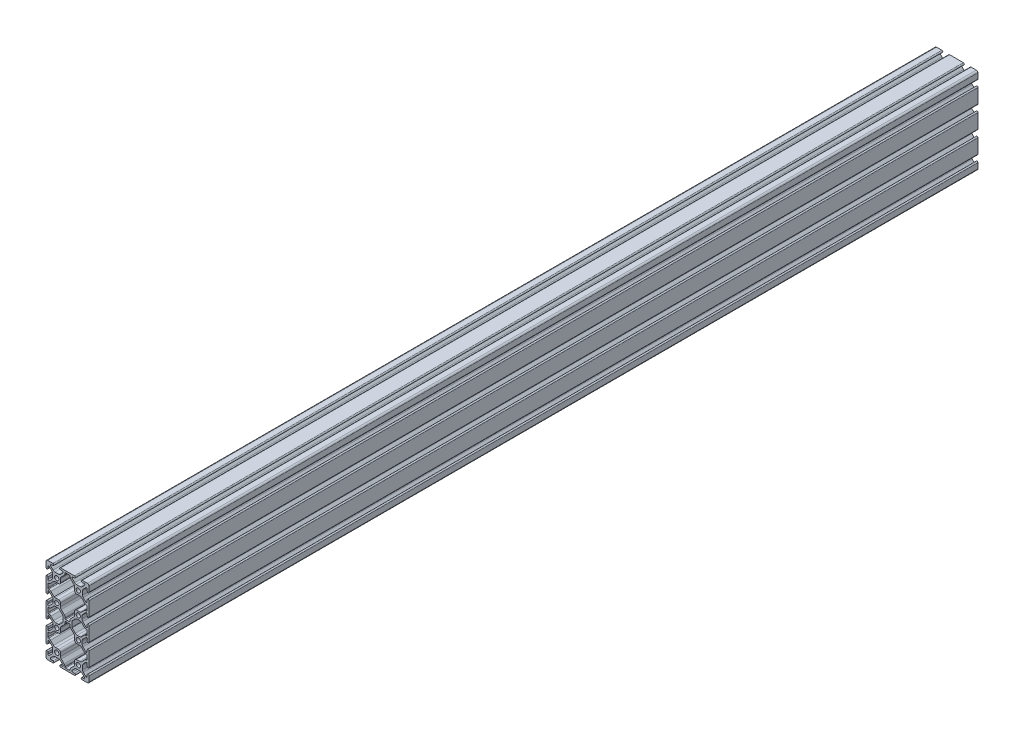
SolidWorks part; units mm, degrees
material "6061 Alloy"
ref_plane "Front Plane" through (0, 0, 0) normal (0, 0, 1) x (1, 0, 0)
ref_plane "Top Plane" through (0, 0, 0) normal (0, 1, 0) x (1, 0, 0)
ref_plane "Right Plane" through (0, 0, 0) normal (1, 0, 0) x (0, 0, -1)
sketch "Sketch1" plane through (0, 0, 0) normal (0, 0, 1) x (1, 0, 0)
  line L0 (-25.6036, 0) -> (0, 0) construction
  line L1 (-8.2025, 43.3108) -> (-5.2383, 46.275)
  line L2 (-25, 3.77) -> (-25, -3.77)
  line L3 (-8.1858, 12.4875) -> (-8.1858, 11.0114)
  line L4 (8.1878, 11.0114) -> (8.1878, 14.5891)
  line L5 (3.7569, 4.9667) -> (7.2705, 8.4802)
  line L6 (14.3225, 16.7991) -> (10.3978, 16.7991)
  line L7 (15.6024, 17.1021) -> (19.2982, 20.7979)
  line L8 (22.1127, 21.7264) -> (21.5397, 21.7264)
  line L9 (-2.3158, 50) -> (2.3158, 50)
  line L10 (22.8749, 26.8568) -> (22.8749, 22.4886)
  line L11 (21.8715, 27.6122) -> (22.1256, 27.6122)
  line L12 (19.7762, 28.7106) -> (16.3874, 32.0994)
  line L13 (13.8398, 33.0305) -> (10.3624, 33.0305)
  line L14 (8.1524, 39.0512) -> (8.1524, 35.2405)
  line L15 (7.2223, 41.2645) -> (4.0122, 44.4746)
  line L16 (3.0895, 47.0978) -> (3.0895, 46.7023)
  line L17 (-22.86, 2.484) -> (-22.86, -2.484)
  line L18 (-5.137, 3.0639) -> (-5.137, -3.0639)
  line L19 (5.137, 3.0639) -> (5.137, -3.0639)
  line L20 (22.86, 2.484) -> (22.86, -2.484)
  line L21 (-5.328, 3.5248) -> (-8.9952, 7.192)
  line L22 (-14.0474, 8.1222) -> (-11.2408, 8.1222)
  line L23 (-16.2931, 7.192) -> (-19.3292, 4.1559)
  line L24 (25, 3.77) -> (25, -3.77)
  line L25 (-22.0978, 3.2462) -> (-21.8437, 3.2462)
  line L26 (-10.3899, 33.0305) -> (-10.3624, 33.0305)
  line L27 (-8.1858, 12.4875) -> (-8.1858, 14.5891)
  line L28 (-8.1524, 39.0512) -> (-8.1524, 35.2405)
  line L29 (-25.6036, -25) -> (3.1162, -25) construction
  line L30 (-12.5, -37.5) -> (-12.5, -51.8721) construction
  line L31 (8.2025, -43.3108) -> (5.2383, -46.275)
  line L32 (-2.8325, -2.6943) -> (-2.8325, -1.8197)
  line L33 (-2.0703, -1.0575) -> (2.0723, -1.0575)
  line L34 (2.8345, -2.6943) -> (2.8345, -1.8197)
  line L35 (-3.7549, -4.9667) -> (-7.2685, -8.4802)
  line L36 (-14.3205, -16.7991) -> (-10.3958, -16.7991)
  line L37 (-15.6004, -17.1021) -> (-19.2962, -20.7979)
  line L38 (-22.1107, -21.7264) -> (-21.5377, -21.7264)
  line L39 (-22.8729, -26.8568) -> (-22.8729, -22.4886)
  line L40 (-22.1107, -27.619) -> (-21.8566, -27.619)
  line L41 (5.328, -3.5248) -> (8.9952, -7.192)
  line L42 (11.2408, -8.1222) -> (14.0474, -8.1222)
  line L43 (16.2931, -7.192) -> (19.3292, -4.1559)
  line L44 (-19.7762, -28.7106) -> (-16.3874, -32.0994)
  line L45 (22.0978, -3.2462) -> (21.8437, -3.2462)
  line L46 (-13.8398, -33.0305) -> (-10.3899, -33.0305)
  line L47 (-7.2223, -41.2645) -> (-4.0122, -44.4746)
  line L48 (5.8948, -47.86) -> (8.0244, -47.86)
  line L49 (-8.0244, 50) -> (-2.3158, 50)
  line L50 (-8.0244, 47.86) -> (-5.8948, 47.86)
  line L51 (0, 47.86) -> (2.3273, 47.86)
  line L52 (-3.0895, -47.0978) -> (-3.0895, -46.7023)
  line L53 (-14.7082, 42.4485) -> (-10.2843, 42.4484)
  line L54 (-16.7975, 43.3108) -> (-19.7617, 46.275)
  line L55 (-19.1052, 47.86) -> (-16.9756, 47.86)
  line L56 (-23.0411, 50) -> (-16.9756, 50)
  line L57 (2.3158, 50) -> (8.0244, 50)
  line L58 (-25, 42.0822) -> (-25, 48.3182)
  line L59 (10.2843, -42.4484) -> (14.7082, -42.4485)
  line L60 (-22.86, 42.0822) -> (-22.86, 44.2118)
  line L61 (-21.1643, 44.6511) -> (-18.3279, 41.8147)
  line L62 (-17.3977, 39.5691) -> (-17.3977, 35.4309)
  line L63 (-18.3279, 33.1853) -> (-21.1271, 30.3861)
  line L64 (-22.86, 31.1039) -> (-22.86, 33.4422)
  line L65 (-25, 33.4422) -> (-25, 29.299)
  line L66 (-25, 21.2197) -> (-25, 29.299)
  line L67 (-25, 17.0404) -> (-25, 21.2197)
  line L68 (-22.8665, 17.0958) -> (-22.8665, 19.4894)
  line L69 (-21.2483, 19.7351) -> (-17.927, 16.4138)
  line L70 (-16.865, 11.3738) -> (-16.865, 14.4803)
  line L71 (-17.7378, 8.7737) -> (-21.0608, 5.4507)
  line L72 (-22.8659, 6.4893) -> (-22.8659, 8.2661)
  line L73 (-25, 3.77) -> (-25, 8.2776)
  line L74 (16.7975, -43.3108) -> (19.7617, -46.275)
  line L75 (19.1052, -47.86) -> (16.9756, -47.86)
  line L76 (16.9756, -50) -> (21.7588, -50)
  line L77 (21.7588, -50) -> (23.0411, -50)
  line L78 (25, -42.0822) -> (25, -48.3182)
  line L79 (22.86, -42.0822) -> (22.86, -44.2118)
  line L80 (21.1643, -44.6511) -> (18.3279, -41.8147)
  line L81 (17.3977, -39.5691) -> (17.3977, -35.4309)
  line L82 (18.3279, -33.1853) -> (21.1271, -30.3861)
  line L83 (25, -33.4422) -> (25, -29.299)
  line L84 (22.86, -31.1039) -> (22.86, -33.4422)
  line L85 (-2.3273, -47.86) -> (0, -47.86)
  line L86 (22.8665, -17.0958) -> (22.8665, -19.4894)
  line L87 (21.2483, -19.7351) -> (17.927, -16.4138)
  line L88 (16.865, -11.3738) -> (16.865, -14.4803)
  line L89 (17.7378, -8.7737) -> (21.0608, -5.4507)
  line L90 (22.8659, -6.4893) -> (22.8659, -8.2661)
  line L91 (25, -21.2197) -> (25, -29.299)
  line L92 (25, -17.0404) -> (25, -21.2197)
  line L93 (25, -3.77) -> (25, -8.2776)
  line L94 (-25, -3.77) -> (-25, -8.2776)
  line L95 (-12.5, 37.5) -> (-12.5, 51.8721) construction
  line L96 (-25.6036, 25) -> (3.1162, 25) construction
  line L97 (-22.8659, -6.4893) -> (-22.8659, -8.2661)
  line L98 (-17.7378, -8.7737) -> (-21.0608, -5.4507)
  line L99 (-16.865, -11.3738) -> (-16.865, -14.4803)
  line L100 (-21.2483, -19.7351) -> (-17.927, -16.4138)
  line L101 (-22.8665, -17.0958) -> (-22.8665, -19.4894)
  line L102 (-25, -17.0404) -> (-25, -21.2197)
  line L103 (-25, -21.2197) -> (-25, -29.299)
  line L104 (-25, -33.4422) -> (-25, -29.299)
  line L105 (-22.86, -31.1039) -> (-22.86, -33.4422)
  line L106 (25, 3.77) -> (25, 8.2776)
  line L107 (25, 17.0404) -> (25, 21.2197)
  line L108 (-18.3279, -33.1853) -> (-21.1271, -30.3861)
  line L109 (-17.3977, -39.5691) -> (-17.3977, -35.4309)
  line L110 (-21.1643, -44.6511) -> (-18.3279, -41.8147)
  line L111 (-22.86, -42.0822) -> (-22.86, -44.2118)
  line L112 (-25, -42.0822) -> (-25, -48.3182)
  line L113 (25, 21.2197) -> (25, 29.299)
  line L114 (2.3158, -50) -> (8.0244, -50)
  line L115 (-23.0411, -50) -> (-16.9756, -50)
  line L116 (22.8659, 6.4893) -> (22.8659, 8.2661)
  line L117 (17.7378, 8.7737) -> (21.0608, 5.4507)
  line L118 (16.865, 11.3738) -> (16.865, 14.4803)
  line L119 (21.2483, 19.7351) -> (17.927, 16.4138)
  line L120 (22.8665, 17.0958) -> (22.8665, 19.4894)
  line L121 (-2.3273, 47.86) -> (0, 47.86)
  line L122 (22.86, 31.1039) -> (22.86, 33.4422)
  line L123 (25, 33.4422) -> (25, 29.299)
  line L124 (-19.1052, -47.86) -> (-16.9756, -47.86)
  line L125 (18.3279, 33.1853) -> (21.1271, 30.3861)
  line L126 (17.3977, 39.5691) -> (17.3977, 35.4309)
  line L127 (21.1643, 44.6511) -> (18.3279, 41.8147)
  line L128 (22.86, 42.0822) -> (22.86, 44.2118)
  line L129 (25, 42.0822) -> (25, 48.3182)
  line L130 (-16.7975, -43.3108) -> (-19.7617, -46.275)
  line L131 (21.7588, 50) -> (23.0411, 50)
  line L132 (16.9756, 50) -> (21.7588, 50)
  line L133 (19.1052, 47.86) -> (16.9756, 47.86)
  line L134 (16.7975, 43.3108) -> (19.7617, 46.275)
  line L135 (10.2843, 42.4484) -> (14.7082, 42.4485)
  line L136 (-14.7082, -42.4485) -> (-10.2843, -42.4484)
  line L137 (-3.0895, 47.0978) -> (-3.0895, 46.7023)
  line L138 (5.8948, 47.86) -> (8.0244, 47.86)
  line L139 (0, -47.86) -> (2.3273, -47.86)
  line L140 (-8.0244, -47.86) -> (-5.8948, -47.86)
  line L141 (-8.0244, -50) -> (-2.3158, -50)
  line L142 (-8.1524, -39.0512) -> (-8.1524, -35.2405)
  line L143 (-8.1858, -12.4875) -> (-8.1858, -14.5891)
  line L144 (-10.3899, -33.0305) -> (-10.3624, -33.0305)
  line L145 (-22.0978, -3.2462) -> (-21.8437, -3.2462)
  line L146 (-16.2931, -7.192) -> (-19.3292, -4.1559)
  line L147 (-14.0474, -8.1222) -> (-11.2408, -8.1222)
  line L148 (-5.328, -3.5248) -> (-8.9952, -7.192)
  line L149 (3.0895, -47.0978) -> (3.0895, -46.7023)
  line L150 (7.2223, -41.2645) -> (4.0122, -44.4746)
  line L151 (8.1524, -39.0512) -> (8.1524, -35.2405)
  line L152 (13.8398, -33.0305) -> (10.3624, -33.0305)
  line L153 (19.7762, -28.7106) -> (16.3874, -32.0994)
  line L154 (-7.2223, 41.2645) -> (-4.0122, 44.4746)
  line L155 (21.8715, -27.6122) -> (22.1256, -27.6122)
  line L156 (22.8749, -26.8568) -> (22.8749, -22.4886)
  line L157 (-2.3158, -50) -> (2.3158, -50)
  line L158 (22.1127, -21.7264) -> (21.5397, -21.7264)
  line L159 (15.6024, -17.1021) -> (19.2982, -20.7979)
  line L160 (-13.8398, 33.0305) -> (-10.3899, 33.0305)
  line L161 (14.3225, -16.7991) -> (10.3978, -16.7991)
  line L162 (22.0978, 3.2462) -> (21.8437, 3.2462)
  line L163 (-19.7762, 28.7106) -> (-16.3874, 32.0994)
  line L164 (16.2931, 7.192) -> (19.3292, 4.1559)
  line L165 (11.2408, 8.1222) -> (14.0474, 8.1222)
  line L166 (5.328, 3.5248) -> (8.9952, 7.192)
  line L167 (3.7569, -4.9667) -> (7.2705, -8.4802)
  line L168 (8.1878, -11.0114) -> (8.1878, -14.5891)
  line L169 (-8.1858, -12.4875) -> (-8.1858, -11.0114)
  line L170 (-8.2025, -43.3108) -> (-5.2383, -46.275)
  line L171 (-22.1107, 27.619) -> (-21.8566, 27.619)
  line L172 (-22.8729, 26.8568) -> (-22.8729, 22.4886)
  line L173 (-22.1107, 21.7264) -> (-21.5377, 21.7264)
  line L174 (-15.6004, 17.1021) -> (-19.2962, 20.7979)
  line L175 (-14.3205, 16.7991) -> (-10.3958, 16.7991)
  line L176 (-3.7549, 4.9667) -> (-7.2685, 8.4802)
  line L177 (2.8345, 2.6943) -> (2.8345, 1.8197)
  line L178 (-2.0703, 1.0575) -> (2.0723, 1.0575)
  line L179 (-2.8325, 2.6943) -> (-2.8325, 1.8197)
  line L180 (25, 0) -> (0, 0) construction
  line L184 (8.2025, 43.3108) -> (5.2383, 46.275)
  arc A0 (-8.1858, 14.5891) -> (-10.3958, 16.7991) centre (-10.3958, 14.5891) ccw
  arc A1 (-8.1524, 35.2405) -> (-10.3624, 33.0305) centre (-10.3624, 35.2405) cw
  arc A2 (10.3978, 16.7991) -> (8.1878, 14.5891) centre (10.3978, 14.5891) ccw
  circle A3 centre (-12.5, 12.5) radius 2.5
  circle A4 centre (-12.5, 37.5) radius 2.5
  arc A5 (7.2705, 8.4802) -> (8.1878, 11.0114) centre (5.0248, 10.7259) ccw
  arc A6 (10.3624, 33.0305) -> (8.1524, 35.2405) centre (10.3624, 35.2405) cw
  arc A7 (14.3225, 16.7991) -> (15.6024, 17.1021) centre (14.2466, 19.974) ccw
  arc A8 (21.5397, 21.7264) -> (19.2982, 20.7979) centre (21.5397, 18.5564) ccw
  arc A9 (22.1127, 21.7264) -> (22.8749, 22.4886) centre (22.1127, 22.4886) ccw
  arc A10 (22.8749, 26.8568) -> (22.1256, 27.6122) centre (22.1127, 26.8501) ccw
  arc A11 (-8.0244, 47.86) -> (-8.0244, 50) centre (-8.0244, 48.93) cw
  arc A12 (19.7762, 28.7106) -> (21.8715, 27.6122) centre (22.1894, 30.7662) ccw
  arc A13 (16.3874, 32.0994) -> (13.8398, 33.0305) centre (13.8398, 29.0797) ccw
  circle A14 centre (12.5, -12.5) radius 2.5
  arc A15 (8.1524, 39.0512) -> (7.2223, 41.2645) centre (4.9767, 39.0188) ccw
  arc A16 (3.0895, 47.0978) -> (2.3273, 47.86) centre (2.3273, 47.0978) ccw
  arc A17 (3.0895, 46.7023) -> (4.0122, 44.4746) centre (6.2399, 46.7023) ccw
  arc A18 (-3.0895, 47.0978) -> (-2.3273, 47.86) centre (-2.3273, 47.0978) cw
  circle A19 centre (12.5, -37.5) radius 2.5
  arc A20 (-3.7549, -4.9667) -> (-2.8325, -2.6943) centre (-5.9826, -2.739) ccw
  arc A21 (-5.137, 3.0639) -> (-5.328, 3.5248) centre (-5.7889, 3.0639) ccw
  arc A22 (-8.9952, 7.192) -> (-11.2408, 8.1222) centre (-11.2408, 4.9464) ccw
  arc A23 (-14.0474, 8.1222) -> (-16.2931, 7.192) centre (-14.0474, 4.9464) ccw
  arc A24 (-21.8437, 3.2462) -> (-19.3292, 4.1559) centre (-21.5569, 6.3836) ccw
  arc A25 (-22.0978, 3.2462) -> (-22.86, 2.484) centre (-22.0978, 2.484) ccw
  arc A26 (-2.0703, -1.0575) -> (-2.8325, -1.8197) centre (-2.0703, -1.8197) ccw
  arc A27 (2.0723, -1.0575) -> (2.8345, -1.8197) centre (2.0723, -1.8197) cw
  arc A28 (3.7569, -4.9667) -> (2.8345, -2.6943) centre (5.9846, -2.739) cw
  arc A29 (-7.2685, -8.4802) -> (-8.1858, -11.0114) centre (-5.0228, -10.7259) ccw
  arc A30 (8.0244, -47.86) -> (8.0244, -50) centre (8.0244, -48.93) cw
  arc A31 (-14.3205, -16.7991) -> (-15.6004, -17.1021) centre (-14.2446, -19.974) ccw
  arc A32 (-21.5377, -21.7264) -> (-19.2962, -20.7979) centre (-21.5377, -18.5564) ccw
  arc A33 (-22.1107, -21.7264) -> (-22.8729, -22.4886) centre (-22.1107, -22.4886) ccw
  arc A34 (-22.8729, -26.8568) -> (-22.1107, -27.619) centre (-22.1107, -26.8568) ccw
  arc A35 (-19.7762, -28.7106) -> (-21.8566, -27.619) centre (-22.1844, -30.772) ccw
  arc A36 (-16.3874, -32.0994) -> (-13.8398, -33.0305) centre (-13.8398, -29.0797) ccw
  arc A37 (5.137, -3.0639) -> (5.328, -3.5248) centre (5.7889, -3.0639) ccw
  arc A38 (8.9952, -7.192) -> (11.2408, -8.1222) centre (11.2408, -4.9464) ccw
  arc A39 (14.0474, -8.1222) -> (16.2931, -7.192) centre (14.0474, -4.9464) ccw
  arc A40 (21.8437, -3.2462) -> (19.3292, -4.1559) centre (21.5569, -6.3836) ccw
  arc A41 (22.0978, -3.2462) -> (22.86, -2.484) centre (22.0978, -2.484) ccw
  arc A42 (5.8948, -47.86) -> (5.2383, -46.275) centre (5.8948, -46.9315) cw
  arc A43 (-8.1524, -39.0512) -> (-7.2223, -41.2645) centre (-4.9767, -39.0188) ccw
  arc A44 (10.2843, -42.4484) -> (8.2025, -43.3108) centre (10.2843, -45.3926) ccw
  arc A45 (16.7975, -43.3108) -> (14.7082, -42.4485) centre (14.7157, -45.3926) ccw
  arc A46 (19.1052, -47.86) -> (19.7617, -46.275) centre (19.1052, -46.9315) ccw
  arc A47 (16.9756, -47.86) -> (16.9756, -50) centre (16.9756, -48.93) ccw
  arc A48 (-5.8948, 47.86) -> (-5.2383, 46.275) centre (-5.8948, 46.9315) cw
  arc A49 (-3.0895, 46.7023) -> (-4.0122, 44.4746) centre (-6.2399, 46.7023) cw
  arc A50 (-10.2843, 42.4484) -> (-8.2025, 43.3108) centre (-10.2843, 45.3926) ccw
  arc A51 (-16.7975, 43.3108) -> (-14.7082, 42.4485) centre (-14.7157, 45.3926) ccw
  arc A52 (-19.1052, 47.86) -> (-19.7617, 46.275) centre (-19.1052, 46.9315) ccw
  arc A53 (-16.9756, 47.86) -> (-16.9756, 50) centre (-16.9756, 48.93) ccw
  arc A54 (-23.0411, 50) -> (-25, 48.3182) centre (-23.0411, 48.0183) ccw
  arc A55 (-25, 42.0822) -> (-22.86, 42.0822) centre (-23.93, 42.0822) ccw
  arc A56 (-21.1643, 44.6511) -> (-22.86, 44.2118) centre (-21.8829, 43.9325) ccw
  arc A57 (-17.3977, 39.5691) -> (-18.3279, 41.8147) centre (-20.5736, 39.5691) ccw
  arc A58 (-18.3279, 33.1853) -> (-17.3977, 35.4309) centre (-20.5736, 35.4309) ccw
  arc A59 (-22.86, 31.1039) -> (-21.1271, 30.3861) centre (-21.8449, 31.1039) ccw
  arc A60 (-22.86, 33.4422) -> (-25, 33.4422) centre (-23.93, 33.4422) ccw
  arc A61 (-25, 17.0404) -> (-22.8665, 17.0958) centre (-23.9321, 17.0236) ccw
  arc A62 (-21.2483, 19.7351) -> (-22.8665, 19.4894) centre (-21.9669, 19.0165) ccw
  arc A63 (-16.865, 14.4803) -> (-17.927, 16.4138) centre (-20.0063, 14.0133) ccw
  arc A64 (-17.7378, 8.7737) -> (-16.865, 11.3738) centre (-20.017, 10.9853) ccw
  arc A65 (-22.8659, 6.4893) -> (-21.0608, 5.4507) centre (-21.9633, 5.97) ccw
  arc A66 (-22.8659, 8.2661) -> (-25, 8.2776) centre (-23.9329, 8.2719) ccw
  arc A67 (23.0411, -50) -> (25, -48.3182) centre (23.0411, -48.0183) ccw
  arc A68 (25, -42.0822) -> (22.86, -42.0822) centre (23.93, -42.0822) ccw
  arc A69 (21.1643, -44.6511) -> (22.86, -44.2118) centre (21.8829, -43.9325) ccw
  arc A70 (17.3977, -39.5691) -> (18.3279, -41.8147) centre (20.5736, -39.5691) ccw
  arc A71 (18.3279, -33.1853) -> (17.3977, -35.4309) centre (20.5736, -35.4309) ccw
  arc A72 (22.86, -31.1039) -> (21.1271, -30.3861) centre (21.8449, -31.1039) ccw
  arc A73 (22.86, -33.4422) -> (25, -33.4422) centre (23.93, -33.4422) ccw
  arc A74 (25, -17.0404) -> (22.8665, -17.0958) centre (23.9321, -17.0236) ccw
  arc A75 (21.2483, -19.7351) -> (22.8665, -19.4894) centre (21.9669, -19.0165) ccw
  arc A76 (16.865, -14.4803) -> (17.927, -16.4138) centre (20.0063, -14.0133) ccw
  arc A77 (17.7378, -8.7737) -> (16.865, -11.3738) centre (20.017, -10.9853) ccw
  arc A78 (22.8659, -6.4893) -> (21.0608, -5.4507) centre (21.9633, -5.97) ccw
  arc A79 (22.8659, -8.2661) -> (25, -8.2776) centre (23.9329, -8.2719) ccw
  arc A80 (-22.8659, -8.2661) -> (-25, -8.2776) centre (-23.9329, -8.2719) cw
  arc A81 (-22.8659, -6.4893) -> (-21.0608, -5.4507) centre (-21.9633, -5.97) cw
  arc A82 (-17.7378, -8.7737) -> (-16.865, -11.3738) centre (-20.017, -10.9853) cw
  arc A83 (-16.865, -14.4803) -> (-17.927, -16.4138) centre (-20.0063, -14.0133) cw
  arc A84 (-21.2483, -19.7351) -> (-22.8665, -19.4894) centre (-21.9669, -19.0165) cw
  arc A85 (-25, -17.0404) -> (-22.8665, -17.0958) centre (-23.9321, -17.0236) cw
  arc A86 (-22.86, -33.4422) -> (-25, -33.4422) centre (-23.93, -33.4422) cw
  arc A87 (-22.86, -31.1039) -> (-21.1271, -30.3861) centre (-21.8449, -31.1039) cw
  arc A88 (-18.3279, -33.1853) -> (-17.3977, -35.4309) centre (-20.5736, -35.4309) cw
  arc A89 (-17.3977, -39.5691) -> (-18.3279, -41.8147) centre (-20.5736, -39.5691) cw
  arc A90 (-21.1643, -44.6511) -> (-22.86, -44.2118) centre (-21.8829, -43.9325) cw
  arc A91 (-25, -42.0822) -> (-22.86, -42.0822) centre (-23.93, -42.0822) cw
  arc A92 (-23.0411, -50) -> (-25, -48.3182) centre (-23.0411, -48.0183) cw
  arc A93 (22.8659, 8.2661) -> (25, 8.2776) centre (23.9329, 8.2719) cw
  arc A94 (22.8659, 6.4893) -> (21.0608, 5.4507) centre (21.9633, 5.97) cw
  arc A95 (17.7378, 8.7737) -> (16.865, 11.3738) centre (20.017, 10.9853) cw
  arc A96 (16.865, 14.4803) -> (17.927, 16.4138) centre (20.0063, 14.0133) cw
  arc A97 (21.2483, 19.7351) -> (22.8665, 19.4894) centre (21.9669, 19.0165) cw
  arc A98 (25, 17.0404) -> (22.8665, 17.0958) centre (23.9321, 17.0236) cw
  arc A99 (22.86, 33.4422) -> (25, 33.4422) centre (23.93, 33.4422) cw
  arc A100 (22.86, 31.1039) -> (21.1271, 30.3861) centre (21.8449, 31.1039) cw
  arc A101 (18.3279, 33.1853) -> (17.3977, 35.4309) centre (20.5736, 35.4309) cw
  arc A102 (17.3977, 39.5691) -> (18.3279, 41.8147) centre (20.5736, 39.5691) cw
  arc A103 (21.1643, 44.6511) -> (22.86, 44.2118) centre (21.8829, 43.9325) cw
  arc A104 (25, 42.0822) -> (22.86, 42.0822) centre (23.93, 42.0822) cw
  arc A105 (23.0411, 50) -> (25, 48.3182) centre (23.0411, 48.0183) cw
  arc A106 (16.9756, 47.86) -> (16.9756, 50) centre (16.9756, 48.93) cw
  arc A107 (19.1052, 47.86) -> (19.7617, 46.275) centre (19.1052, 46.9315) cw
  arc A108 (16.7975, 43.3108) -> (14.7082, 42.4485) centre (14.7157, 45.3926) cw
  arc A109 (10.2843, 42.4484) -> (8.2025, 43.3108) centre (10.2843, 45.3926) cw
  arc A110 (-8.1524, 39.0512) -> (-7.2223, 41.2645) centre (-4.9767, 39.0188) cw
  arc A111 (5.8948, 47.86) -> (5.2383, 46.275) centre (5.8948, 46.9315) ccw
  arc A112 (-16.9756, -47.86) -> (-16.9756, -50) centre (-16.9756, -48.93) cw
  arc A113 (-19.1052, -47.86) -> (-19.7617, -46.275) centre (-19.1052, -46.9315) cw
  arc A114 (-16.7975, -43.3108) -> (-14.7082, -42.4485) centre (-14.7157, -45.3926) cw
  arc A115 (-10.2843, -42.4484) -> (-8.2025, -43.3108) centre (-10.2843, -45.3926) cw
  arc A116 (-3.0895, -46.7023) -> (-4.0122, -44.4746) centre (-6.2399, -46.7023) ccw
  arc A117 (-5.8948, -47.86) -> (-5.2383, -46.275) centre (-5.8948, -46.9315) ccw
  arc A118 (-22.0978, -3.2462) -> (-22.86, -2.484) centre (-22.0978, -2.484) cw
  arc A119 (-21.8437, -3.2462) -> (-19.3292, -4.1559) centre (-21.5569, -6.3836) cw
  arc A120 (-14.0474, -8.1222) -> (-16.2931, -7.192) centre (-14.0474, -4.9464) cw
  arc A121 (-8.9952, -7.192) -> (-11.2408, -8.1222) centre (-11.2408, -4.9464) cw
  arc A122 (-5.137, -3.0639) -> (-5.328, -3.5248) centre (-5.7889, -3.0639) cw
  arc A123 (-3.0895, -47.0978) -> (-2.3273, -47.86) centre (-2.3273, -47.0978) ccw
  arc A124 (3.0895, -46.7023) -> (4.0122, -44.4746) centre (6.2399, -46.7023) cw
  arc A125 (3.0895, -47.0978) -> (2.3273, -47.86) centre (2.3273, -47.0978) cw
  arc A126 (8.1524, -39.0512) -> (7.2223, -41.2645) centre (4.9767, -39.0188) cw
  arc A127 (16.3874, -32.0994) -> (13.8398, -33.0305) centre (13.8398, -29.0797) cw
  arc A128 (19.7762, -28.7106) -> (21.8715, -27.6122) centre (22.1894, -30.7662) cw
  arc A129 (-8.0244, -47.86) -> (-8.0244, -50) centre (-8.0244, -48.93) ccw
  arc A130 (22.8749, -26.8568) -> (22.1256, -27.6122) centre (22.1127, -26.8501) cw
  arc A131 (22.1127, -21.7264) -> (22.8749, -22.4886) centre (22.1127, -22.4886) cw
  arc A132 (21.5397, -21.7264) -> (19.2982, -20.7979) centre (21.5397, -18.5564) cw
  arc A133 (14.3225, -16.7991) -> (15.6024, -17.1021) centre (14.2466, -19.974) cw
  arc A134 (22.0978, 3.2462) -> (22.86, 2.484) centre (22.0978, 2.484) cw
  arc A135 (21.8437, 3.2462) -> (19.3292, 4.1559) centre (21.5569, 6.3836) cw
  arc A136 (14.0474, 8.1222) -> (16.2931, 7.192) centre (14.0474, 4.9464) cw
  arc A137 (8.9952, 7.192) -> (11.2408, 8.1222) centre (11.2408, 4.9464) cw
  arc A138 (5.137, 3.0639) -> (5.328, 3.5248) centre (5.7889, 3.0639) cw
  arc A139 (10.3624, -33.0305) -> (8.1524, -35.2405) centre (10.3624, -35.2405) ccw
  arc A140 (7.2705, -8.4802) -> (8.1878, -11.0114) centre (5.0248, -10.7259) cw
  circle A141 centre (-12.5, -37.5) radius 2.5
  arc A142 (-16.3874, 32.0994) -> (-13.8398, 33.0305) centre (-13.8398, 29.0797) cw
  arc A143 (-19.7762, 28.7106) -> (-21.8566, 27.619) centre (-22.1844, 30.772) cw
  arc A144 (-22.8729, 26.8568) -> (-22.1107, 27.619) centre (-22.1107, 26.8568) cw
  arc A145 (-22.1107, 21.7264) -> (-22.8729, 22.4886) centre (-22.1107, 22.4886) cw
  arc A146 (-21.5377, 21.7264) -> (-19.2962, 20.7979) centre (-21.5377, 18.5564) cw
  arc A147 (-14.3205, 16.7991) -> (-15.6004, 17.1021) centre (-14.2446, 19.974) cw
  arc A148 (8.0244, 47.86) -> (8.0244, 50) centre (8.0244, 48.93) ccw
  circle A149 centre (-12.5, -12.5) radius 2.5
  arc A150 (-7.2685, 8.4802) -> (-8.1858, 11.0114) centre (-5.0228, 10.7259) cw
  arc A151 (3.7569, 4.9667) -> (2.8345, 2.6943) centre (5.9846, 2.739) ccw
  arc A152 (2.0723, 1.0575) -> (2.8345, 1.8197) centre (2.0723, 1.8197) ccw
  arc A153 (-2.0703, 1.0575) -> (-2.8325, 1.8197) centre (-2.0703, 1.8197) cw
  arc A154 (-3.7549, 4.9667) -> (-2.8325, 2.6943) centre (-5.9826, 2.739) cw
  circle A155 centre (12.5, 37.5) radius 2.5
  circle A156 centre (12.5, 12.5) radius 2.5
  arc A157 (10.3978, -16.7991) -> (8.1878, -14.5891) centre (10.3978, -14.5891) cw
  arc A158 (-8.1524, -35.2405) -> (-10.3624, -33.0305) centre (-10.3624, -35.2405) ccw
  arc A159 (-8.1858, -14.5891) -> (-10.3958, -16.7991) centre (-10.3958, -14.5891) cw
  point P0 (-5.137, 0)
  point P2 (-25, 0)
  point P3 (-22.86, 0)
  point P5 (5.137, 0)
  point P511 (22.86, 0)
  dimension "D3" = 6.5
  dimension "D4" = 14.86
  dimension "D6" = 5
  dimension "D7" = 25
  dimension "D10" = 2.21
  dimension "D12" = 2.14
  dimension "D2" = 0.7622
  dimension "D5" = 0.7622
  dimension "D8" = 2.21
  dimension "D11" = 2.21
  dimension "D13" = 2.21
  dimension "D14" = 3.17
  dimension "D15" = 3.17
  dimension "D16" = 3.17
  dimension "D17" = 3.17
  dimension "D9" = 2.14
  dimension "D18" = 100
  dimension "D19" = 50
extrude "Extrude1" add sketch "Sketch1" against normal blind 1031.698
